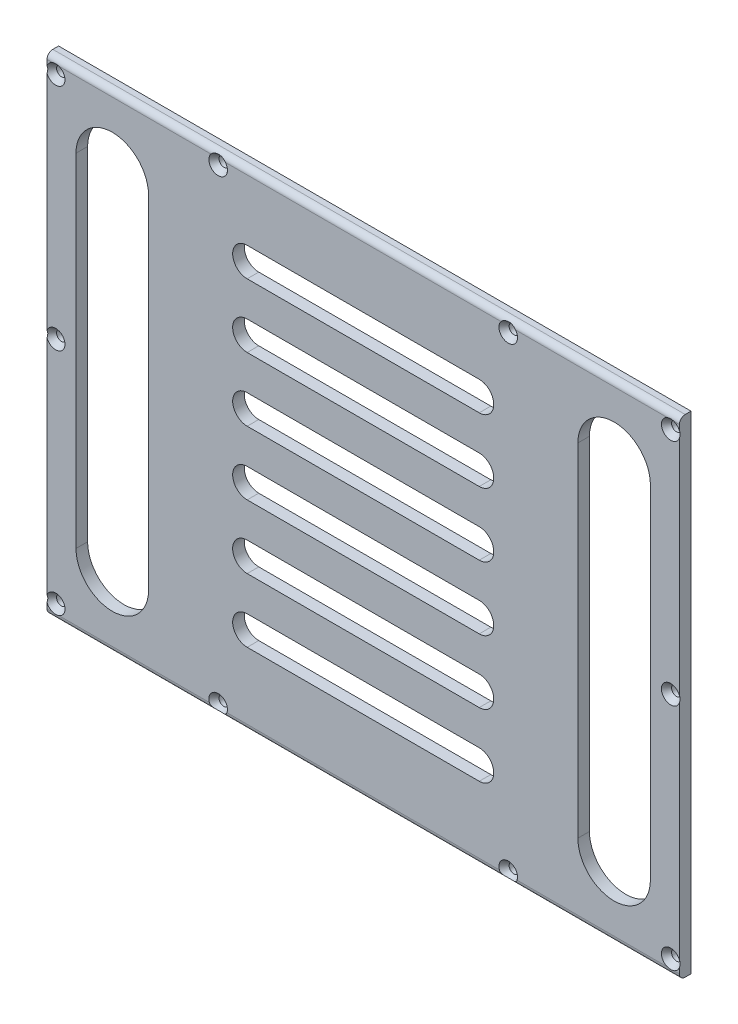
SolidWorks part; units mm, degrees
ref_plane "Front Plane" through (0, 0, 0) normal (1, 0, 0) x (0, 1, 0)
ref_plane "Top Plane" through (0, 0, 0) normal (0, 0, 1) x (0, 1, 0)
ref_plane "Right Plane" through (0, 0, 0) normal (0, 1, 0) x (-1, 0, 0)
sketch "Sketch1" plane through (0, 0, 0) normal (0, 0, 1) x (0, 1, 0)
  line L0 (84, 218) -> (84, 0) construction
  line L1 (0, 0) -> (168, 0)
  line L2 (0, 0) -> (0, 218)
  line L3 (0, 218) -> (168, 218)
  line L4 (168, 0) -> (168, 218)
  line L5 (30, 149) -> (30, 69) construction
  line L14 (35, 149) -> (35, 69)
  line L15 (25, 149) -> (25, 69)
  line L16 (0, 109) -> (191, 109) construction
  line L17 (52, 149) -> (52, 69) construction
  line L18 (57, 149) -> (57, 69)
  line L19 (47, 149) -> (47, 69)
  line L20 (74, 149) -> (74, 69) construction
  line L21 (79, 149) -> (79, 69)
  line L22 (69, 149) -> (69, 69)
  line L23 (96, 149) -> (96, 69) construction
  line L24 (101, 149) -> (101, 69)
  line L25 (91, 149) -> (91, 69)
  line L26 (118, 149) -> (118, 69) construction
  line L27 (123, 149) -> (123, 69)
  line L28 (113, 149) -> (113, 69)
  line L29 (140, 149) -> (140, 69) construction
  line L30 (145, 149) -> (145, 69)
  line L31 (135, 149) -> (135, 69)
  line L32 (25, 195.5) -> (143, 195.5) construction
  line L35 (25, 208) -> (143, 208)
  line L36 (25, 183) -> (143, 183)
  line L37 (25, 22.5) -> (143, 22.5) construction
  line L38 (25, 35) -> (143, 35)
  line L39 (25, 10) -> (143, 10)
  line L110 (162, 151) -> (162, 71) construction
  line L111 (167, 151) -> (167, 71)
  line L112 (157, 151) -> (157, 71)
  line L113 (162, 149) -> (162, 69) construction
  line L114 (167, 149) -> (167, 69)
  line L115 (157, 149) -> (157, 69)
  circle A0 centre (5, 3) radius 1.7
  circle A1 centre (5, 215) radius 1.7
  circle A2 centre (163, 215) radius 1.7
  circle A3 centre (163, 3) radius 1.7
  circle A4 centre (84, 215) radius 1.7
  circle A5 centre (84, 3) radius 1.7
  arc A6 (35, 149) -> (25, 149) centre (30, 149) ccw
  arc A7 (25, 69) -> (35, 69) centre (30, 69) ccw
  arc A8 (57, 149) -> (47, 149) centre (52, 149) ccw
  arc A9 (47, 69) -> (57, 69) centre (52, 69) ccw
  arc A10 (79, 149) -> (69, 149) centre (74, 149) ccw
  arc A11 (69, 69) -> (79, 69) centre (74, 69) ccw
  arc A12 (101, 149) -> (91, 149) centre (96, 149) ccw
  arc A13 (91, 69) -> (101, 69) centre (96, 69) ccw
  arc A14 (123, 149) -> (113, 149) centre (118, 149) ccw
  arc A15 (113, 69) -> (123, 69) centre (118, 69) ccw
  arc A16 (145, 149) -> (135, 149) centre (140, 149) ccw
  arc A17 (135, 69) -> (145, 69) centre (140, 69) ccw
  circle A20 centre (3, 59) radius 1.7
  circle A21 centre (164, 59) radius 1.7
  circle A22 centre (164, 159) radius 1.7
  circle A23 centre (3, 159) radius 1.7
  arc A24 (25, 208) -> (25, 183) centre (25, 195.5) ccw
  arc A25 (143, 183) -> (143, 208) centre (143, 195.5) ccw
  arc A26 (25, 35) -> (25, 10) centre (25, 22.5) ccw
  arc A27 (143, 10) -> (143, 35) centre (143, 22.5) ccw
  arc A76 (167, 149) -> (157, 149) centre (162, 149) ccw
  arc A77 (157, 69) -> (167, 69) centre (162, 69) ccw
  point P20 (162, 76)
  point P21 (84, 195.5)
  point P29 (30, 109)
  point P37 (0, 109)
  point P41 (52, 109)
  point P48 (74, 109)
  point P55 (96, 109)
  point P62 (118, 109)
  point P69 (140, 109)
  point P74 (84, 22.5)
  point P89 (162, 76)
  point P96 (162, 76)
  point P103 (162, 76)
  point P110 (162, 78)
  point P117 (162, 78)
  point P124 (162, 78)
  point P131 (162, 78)
  point P138 (162, 78)
  point P145 (162, 78)
  point P152 (162, 78)
  point P159 (162, 78)
  point P166 (162, 78)
  point P173 (162, 78)
  point P180 (162, 103)
  point P187 (162, 103)
  point P194 (162, 103)
  point P201 (162, 103)
  point P208 (162, 111)
  point P215 (162, 111)
  point P222 (162, 111)
  point P229 (162, 111)
  point P236 (162, 111)
  point P243 (162, 111)
  point P250 (162, 111)
  point P257 (162, 111)
  point P264 (162, 109)
  dimension "D7" = 3.4
  dimension "D1" = 168
  dimension "D2" = 218
  dimension "D3" = 3
  dimension "D4" = 5
  dimension "D5" = 3
  dimension "D6" = 5
  dimension "D13" = 10
  dimension "D14" = 80
  dimension "D16" = 12
  dimension "D8" = 25
  dimension "D9" = 50
  dimension "D10" = 4
  dimension "D11" = 3
  dimension "D12" = 10
  dimension "D17" = 25
  dimension "D15" = 7
extrude "Boss-Extrude2" add sketch "Sketch1" along normal blind 4
chamfer "Chamfer1" distance 1.5 distance2 2 10 edges at (-57.3, 3, 4) (-57.3, 164, 4) (-157.3, 164, 4) (-213.3, 163, 4) (-1.3, 163, 4) (-1.3, 84, 4) (-213.3, 84, 4) (-213.3, 5, 4) (-157.3, 3, 4) (-1.3, 5, 4)
fillet "Fillet1" radius 2 2 edges at (-109, 168, 4) (-109, 0, 4)
equation "\"MotorDriverLength\"= 60mm"
equation "\"MotorLength\"= 60"
equation "\"MotorDriverWidth\"=44"
equation "\"MotorWidth\"= 37"
equation "\"InnerWallThickness\"=3"
equation "\"BatteryWidth\"= 60"
equation "\"OuterWallThickness\" = 6"
equation "\"CompartmentHeight\"=37"
equation "\"CompartmentWidth\"= \"MotorDriverLength\""
equation "\"MotorDiameter\"=37"
equation "\"BatteryHeight\"=24.2019"
equation "\"MotorDriverHeight\"=28"
equation "\"CircuitHeight\"=30"
equation "\"FanThickness\"= 10"
equation "\"FanHeight\"=50"
equation "\"MotorShaftHole\"=12"
equation "\"BearingBore\"=4"
equation "\"MinShinWidth\"= 20"
equation "\"ShinThickness\"=10"
equation "\"PivotDistance\"=30"
equation "\"ThighLength\"= 200"
equation "\"KneeLength\" =20"
equation "\"HipBore\"=27"
equation "\"ThighThickness\"=20"
equation "\"MaxBending\"=135"
equation "\"MaxStretchingAngle\"= 140"
equation "\"ThighJointDistance\"=157.485"
equation "\"ShinLength\"=120"
equation "\"BearingDiameter\"= 10"
equation "\"CircuitLength\"=50"
equation "\"ChessisInnerWidth\"= \"OuterWallThickness\" * 2 + \"MotorDriverLength\" + \"MotorDiameter\" + \"InnerWallThickness\" * 3 + \"CircuitLength\""
equation "\"D1@Sketch1\"=\"ChessisInnerWidth\""
equation "\"D2@Sketch1\"=\"ChassisWidth\"+\"OuterWallThickness\"*2"
equation "\"D11@Sketch1\"=\"OuterWallThickness\"/2"
equation "\"D3@Sketch1\"=\"OuterWallThickness\"/2"
equation "\"D5@Sketch1\"=\"OuterWallThickness\"/2"
equation "\"ChessisHeight\"= \"BatteryHeight\" + 10 + \"InnerWallThickness\" + \"MotorDiameter\" + 10 + \"OuterWallThickness\" * 2"
equation "\"ChassisWidth\"= \"MotorDriverWidth\"*4+30"
